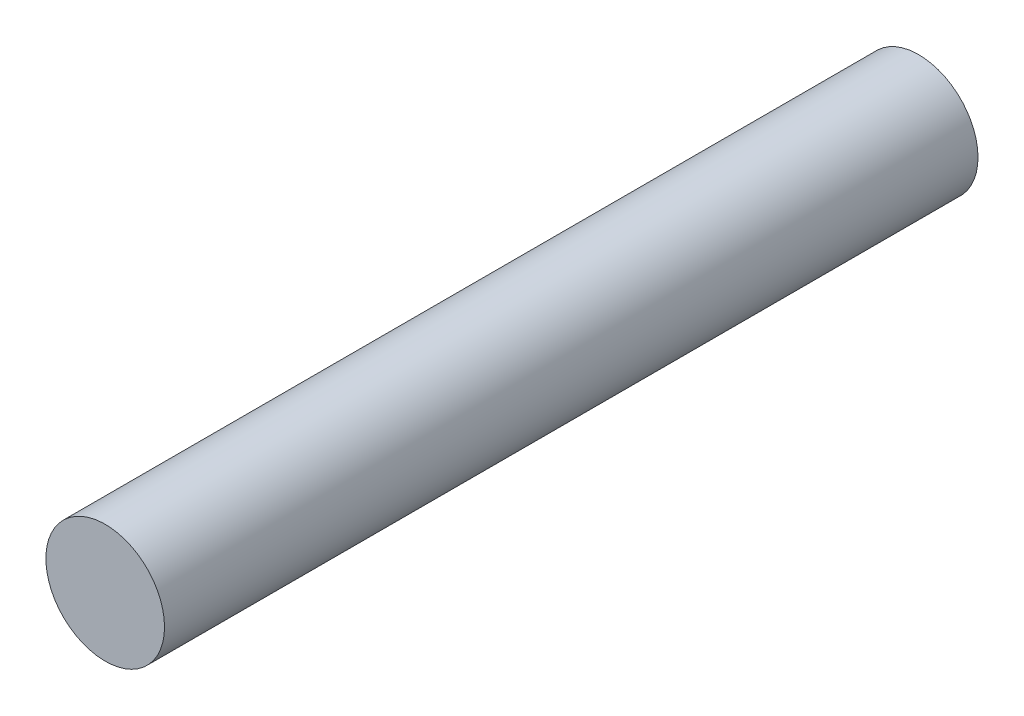
SolidWorks part; units mm, degrees
ref_plane "Front Plane" through (0, 0, 0) normal (0, 0, 1) x (1, 0, 0)
ref_plane "Top Plane" through (0, 0, 0) normal (0, 1, 0) x (1, 0, 0)
ref_plane "Right Plane" through (0, 0, 0) normal (1, 0, 0) x (0, 0, -1)
sketch "Sketch1" plane through (0, 0, 0) normal (0, 0, 1) x (1, 0, 0)
  circle A1 centre (-3.25, -0.25) radius 0.875
  circle A2 centre (-3.25, -0.25) radius 0.875
  dimension "D1" = 0
extrude "Boss-Extrude1" add sketch "Sketch1" along normal blind 12
